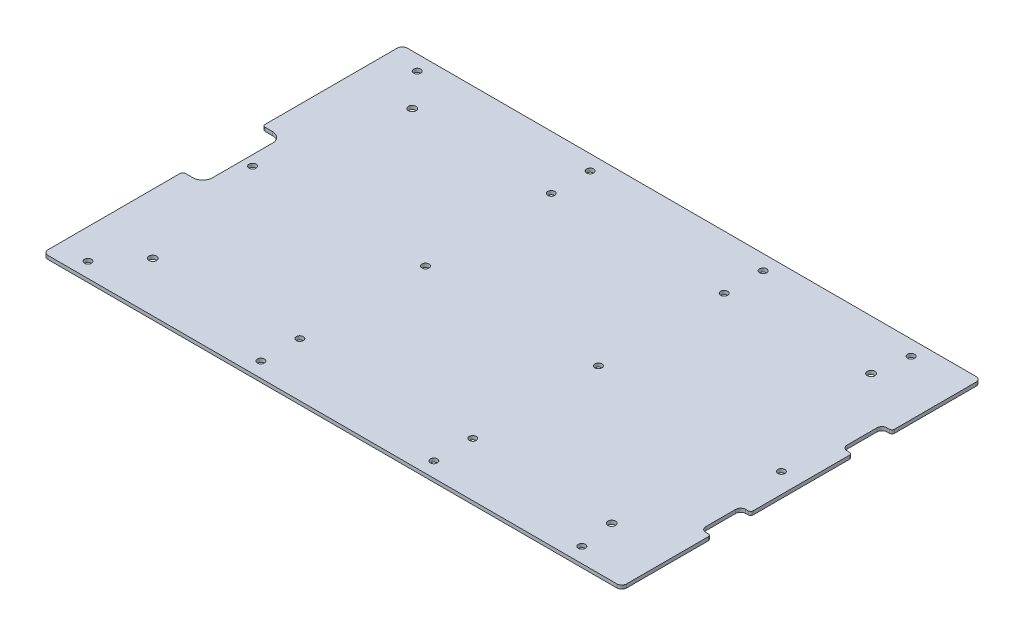
SolidWorks part; units mm, degrees
material "1060 Alloy"
ref_plane "Front" through (0, 0, 0) normal (0, 0, 1) x (1, 0, 0)
ref_plane "Top" through (0, 0, 0) normal (0, 1, 0) x (1, 0, 0)
ref_plane "Right" through (0, 0, 0) normal (1, 0, 0) x (0, 0, -1)
sketch "Sketch1" plane through (0, 0, 0) normal (0, 1, 0) x (1, 0, 0)
  line L0 (-55.0333, 0) -> (-165.1, 0) construction
  line L1 (-180.975, 114.3) -> (180.975, 114.3)
  line L2 (-184.15, 111.125) -> (-184.15, -111.125)
  line L3 (-180.975, -114.3) -> (180.975, -114.3)
  line L4 (184.15, 111.125) -> (184.15, -111.125)
  line L5 (-184.15, 114.3) -> (184.15, -114.3) construction
  line L6 (-184.15, -114.3) -> (184.15, 114.3) construction
  line L7 (-165.1, -104.775) -> (165.1, -104.775) construction
  line L8 (-165.1, -104.775) -> (-165.1, 104.775) construction
  line L9 (-165.1, 104.775) -> (165.1, 104.775) construction
  line L10 (165.1, -104.775) -> (165.1, 104.775) construction
  line L11 (-165.1, -104.775) -> (165.1, 104.775) construction
  line L12 (-165.1, 104.775) -> (165.1, -104.775) construction
  line L13 (-55.0333, -104.775) -> (55.0333, -104.775) construction
  line L14 (-55.0333, -104.775) -> (-55.0333, 104.775) construction
  line L15 (-55.0333, 104.775) -> (55.0333, 104.775) construction
  line L16 (55.0333, -104.775) -> (55.0333, 104.775) construction
  line L17 (-55.0333, -104.775) -> (55.0333, 104.775) construction
  line L18 (-55.0333, 104.775) -> (55.0333, -104.775) construction
  line L19 (55.0333, 0) -> (165.1, 0) construction
  line L20 (-55.0333, 0) -> (55.0333, 0) construction
  line L31 (-55.0291, 80.01) -> (55.0291, 80.01) construction
  line L32 (149.225, -104.775) -> (149.225, 104.775) construction
  line L33 (-55.0291, 80.01) -> (-55.0291, -80.01) construction
  line L34 (-55.0291, -80.01) -> (55.0291, -80.01) construction
  line L35 (55.0291, 80.01) -> (55.0291, -80.01) construction
  line L36 (-55.0291, 80.01) -> (55.0291, -80.01) construction
  line L37 (-55.0291, -80.01) -> (55.0291, 80.01) construction
  circle A0 centre (-165.1, 104.775) radius 2.2479
  circle A1 centre (-55.0333, 104.775) radius 2.2479
  circle A2 centre (55.0333, 104.775) radius 2.2479
  circle A3 centre (165.1, 104.775) radius 2.2479 construction
  circle A4 centre (165.1, -104.775) radius 2.2479 construction
  circle A5 centre (55.0333, -104.775) radius 2.2479
  circle A6 centre (-55.0333, -104.775) radius 2.2479
  circle A7 centre (-165.1, -104.775) radius 2.2479
  circle A12 centre (-55.0333, 0) radius 2.2479
  circle A13 centre (55.0333, 0) radius 2.2479
  arc A14 (184.15, 111.125) -> (180.975, 114.3) centre (180.975, 111.125) ccw
  arc A15 (184.15, -111.125) -> (180.975, -114.3) centre (180.975, -111.125) cw
  arc A16 (-180.975, -114.3) -> (-184.15, -111.125) centre (-180.975, -111.125) cw
  arc A17 (-180.975, 114.3) -> (-184.15, 111.125) centre (-180.975, 111.125) ccw
  circle A24 centre (149.225, -104.775) radius 2.2479
  circle A25 centre (149.225, 104.775) radius 2.2479
  circle A26 centre (55.0291, -80.01) radius 2.2479
  circle A27 centre (-55.0291, -80.01) radius 2.2479
  circle A28 centre (-55.0291, 80.01) radius 2.2479
  circle A29 centre (55.0291, 80.01) radius 2.2479
  circle A30 centre (171.45, 0) radius 2.2479
  circle A31 centre (-165.1, 0) radius 2.2479
  circle A32 centre (-146.05, 82.55) radius 2.4574 construction
  circle A33 centre (-146.05, 82.55) radius 2.4575
  circle A34 centre (146.05, 82.55) radius 2.4574 construction
  circle A35 centre (146.05, 82.55) radius 2.4575
  circle A36 centre (-146.05, -82.55) radius 2.4574 construction
  circle A37 centre (-146.05, -82.55) radius 2.4575
  circle A38 centre (146.05, -82.55) radius 2.4574 construction
  circle A39 centre (146.05, -82.55) radius 2.4575
  point P0 (0, 0)
  point P6 (0, 0)
  point P11 (0, 0)
  point P28 (0, 0)
  point P29 (0, 0)
  point P32 (0, 0)
  dimension "D5" = 4.4958
  dimension "D8" = 4.4958
  dimension "D11" = 3.175
  dimension "D10" = 12.7
  dimension "D12" = 19.05
  dimension "D13" = 110.0667
  dimension "D1" = 368.3
  dimension "D2" = 228.6
  dimension "D3" = 9.525
  dimension "D4" = 19.05
  dimension "D6" = 160.02
  dimension "D7" = 34.925
  dimension "D9" = 110.0582
extrude "Boss-Extrude1" add sketch "Sketch1" along normal blind 2.286
sketch "Sketch2" plane through (0, 0, 0) normal (0, -1, 0) x (1, 0, 0)
  line L5 (184.15, 111.125) -> (184.15, -111.125) construction
  line L6 (184.15, 57.658) -> (180.975, 57.658)
  line L7 (184.15, 57.658) -> (184.15, 32.258)
  line L8 (184.15, 32.258) -> (180.975, 32.258)
  line L9 (177.8, 54.483) -> (177.8, 35.433)
  line L10 (-184.15, 0) -> (188.1505, 0) construction
  line L11 (-184.15, -111.125) -> (-184.15, 111.125) construction
  line L12 (188.1505, -117.475) -> (188.1505, 117.475) construction
  line L13 (177.8, 44.958) -> (184.15, 44.958) construction
  line L14 (184.15, -32.258) -> (180.975, -32.258)
  line L15 (184.15, -57.658) -> (184.15, -32.258)
  line L16 (177.8, -54.483) -> (177.8, -35.433)
  line L17 (184.15, -57.658) -> (180.975, -57.658)
  line L19 (-184.15, 25.4) -> (-177.8, 25.4)
  line L20 (-184.15, 25.4) -> (-184.15, -25.4)
  line L21 (-184.15, -25.4) -> (-177.8, -25.4)
  line L22 (-171.45, 19.05) -> (-171.45, -19.05)
  arc A0 (180.975, -57.658) -> (177.8, -54.483) centre (180.975, -54.483) cw
  arc A1 (177.8, -35.433) -> (180.975, -32.258) centre (180.975, -35.433) cw
  arc A2 (177.8, 35.433) -> (180.975, 32.258) centre (180.975, 35.433) ccw
  arc A3 (177.8, 54.483) -> (180.975, 57.658) centre (180.975, 54.483) cw
  arc A4 (-171.45, -19.05) -> (-177.8, -25.4) centre (-177.8, -19.05) cw
  arc A5 (-171.45, 19.05) -> (-177.8, 25.4) centre (-177.8, 19.05) ccw
  point P20 (177.8, -57.658)
  point P23 (177.8, -32.258)
  point P26 (177.8, 32.258)
  point P29 (177.8, 57.658)
  point P38 (-171.45, 25.4)
  dimension "D4" = 3.175
  dimension "D7" = 6.35
  dimension "D1" = 25.4
  dimension "D2" = 44.958
  dimension "D3" = 6.35
  dimension "D5" = 50.8
  dimension "D6" = 12.7
extrude "Cut-Extrude1" cut sketch "Sketch2" against normal through all
fillet "Fillet1" radius 1.5875 6 edges at (184.15, 1.143, -57.658) (184.15, 1.143, -32.258) (184.15, 1.143, 32.258) (184.15, 1.143, 57.658) (-184.15, 1.143, -25.4) (-184.15, 1.143, 25.4)
sketch "Sketch3" [suppressed] plane through (0, 2.286, 0) normal (0, 1, 0) x (1, 0, 0)
  line L0 (-198.0256, -111.0509) -> (-198.0256, 117.5491)
  line L1 (204.2781, -126.2696) -> (-1014.9219, -126.2696)
  line L2 (204.2781, -126.2696) -> (204.2781, 1092.9304)
  line L3 (204.2781, 1092.9304) -> (-1014.9219, 1092.9304)
  line L4 (-1014.9219, -126.2696) -> (-1014.9219, 1092.9304)
  line L5 (182.9744, -111.0509) -> (-185.3256, -111.0509)
  line L6 (182.9744, -111.0509) -> (182.9744, 117.5491)
  line L7 (182.9744, 117.5491) -> (-185.3256, 117.5491)
  line L8 (-185.3256, -111.0509) -> (-185.3256, 117.5491)
  line L9 (-198.0256, -111.0509) -> (-566.3256, -111.0509)
  line L10 (-566.3256, -111.0509) -> (-566.3256, 117.5491)
  line L11 (-198.0256, 117.5491) -> (-566.3256, 117.5491)
  line L12 (-579.0256, -111.0509) -> (-579.0256, 117.5491)
  line L13 (-579.0256, -111.0509) -> (-947.3256, -111.0509)
  line L14 (-947.3256, -111.0509) -> (-947.3256, 117.5491)
  line L15 (-579.0256, 117.5491) -> (-947.3256, 117.5491)
  line L16 (-198.0256, 130.2491) -> (-198.0256, 358.8491)
  line L17 (-198.0256, 130.2491) -> (-566.3256, 130.2491)
  line L18 (-566.3256, 130.2491) -> (-566.3256, 358.8491)
  line L19 (-198.0256, 358.8491) -> (-566.3256, 358.8491)
  line L20 (-579.0256, 130.2491) -> (-579.0256, 358.8491)
  line L21 (-579.0256, 130.2491) -> (-947.3256, 130.2491)
  line L22 (-947.3256, 130.2491) -> (-947.3256, 358.8491)
  line L23 (-579.0256, 358.8491) -> (-947.3256, 358.8491)
  line L24 (-198.0256, 371.5491) -> (-198.0256, 600.1491)
  line L25 (-198.0256, 371.5491) -> (-566.3256, 371.5491)
  line L26 (-566.3256, 371.5491) -> (-566.3256, 600.1491)
  line L27 (-198.0256, 600.1491) -> (-566.3256, 600.1491)
  line L28 (-579.0256, 371.5491) -> (-579.0256, 600.1491)
  line L29 (-579.0256, 371.5491) -> (-947.3256, 371.5491)
  line L30 (-947.3256, 371.5491) -> (-947.3256, 600.1491)
  line L31 (-579.0256, 600.1491) -> (-947.3256, 600.1491)
  line L32 (-198.0256, 612.8491) -> (-198.0256, 841.4491)
  line L33 (-198.0256, 612.8491) -> (-566.3256, 612.8491)
  line L34 (-566.3256, 612.8491) -> (-566.3256, 841.4491)
  line L35 (-198.0256, 841.4491) -> (-566.3256, 841.4491)
  line L36 (-579.0256, 612.8491) -> (-579.0256, 841.4491)
  line L37 (-579.0256, 612.8491) -> (-947.3256, 612.8491)
  line L38 (-947.3256, 612.8491) -> (-947.3256, 841.4491)
  line L39 (-579.0256, 841.4491) -> (-947.3256, 841.4491)
  line L40 (-198.0256, 854.1491) -> (-198.0256, 1082.7491)
  line L41 (-198.0256, 854.1491) -> (-566.3256, 854.1491)
  line L42 (-566.3256, 854.1491) -> (-566.3256, 1082.7491)
  line L43 (-198.0256, 1082.7491) -> (-566.3256, 1082.7491)
  line L44 (-579.0256, 854.1491) -> (-579.0256, 1082.7491)
  line L45 (-579.0256, 854.1491) -> (-947.3256, 854.1491)
  line L46 (-947.3256, 854.1491) -> (-947.3256, 1082.7491)
  line L47 (-579.0256, 1082.7491) -> (-947.3256, 1082.7491)
  line L48 (182.9744, 130.2491) -> (182.9744, 358.8491)
  line L49 (182.9744, 130.2491) -> (-185.3256, 130.2491)
  line L50 (-185.3256, 130.2491) -> (-185.3256, 358.8491)
  line L51 (182.9744, 358.8491) -> (-185.3256, 358.8491)
  line L52 (182.9744, 371.5491) -> (182.9744, 600.1491)
  line L53 (182.9744, 371.5491) -> (-185.3256, 371.5491)
  line L54 (-185.3256, 371.5491) -> (-185.3256, 600.1491)
  line L55 (182.9744, 600.1491) -> (-185.3256, 600.1491)
  line L56 (182.9744, 612.8491) -> (182.9744, 841.4491)
  line L57 (182.9744, 612.8491) -> (-185.3256, 612.8491)
  line L58 (-185.3256, 612.8491) -> (-185.3256, 841.4491)
  line L59 (182.9744, 841.4491) -> (-185.3256, 841.4491)
  line L60 (182.9744, 854.1491) -> (182.9744, 1082.7491)
  line L61 (182.9744, 854.1491) -> (-185.3256, 854.1491)
  line L62 (-185.3256, 854.1491) -> (-185.3256, 1082.7491)
  line L63 (182.9744, 1082.7491) -> (-185.3256, 1082.7491)
  dimension "D1" = 1219.2
  dimension "D2" = 1219.2
  dimension "D3" = 368.3
  dimension "D4" = 228.6
  dimension "D5" = 3
  dimension "D6" = 5
